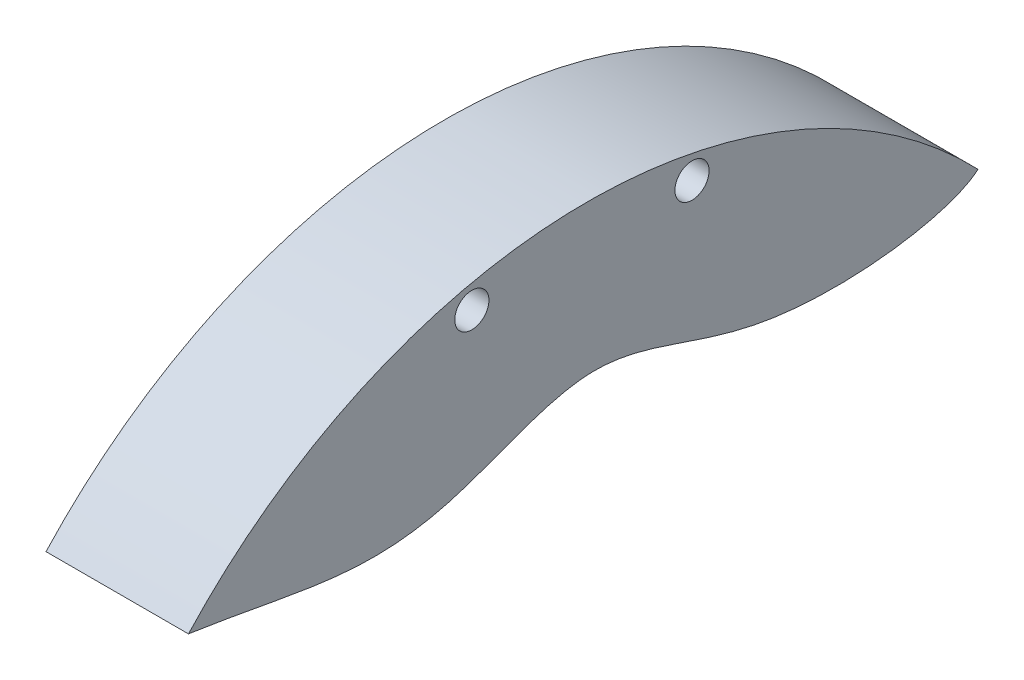
SolidWorks part; units mm, degrees
ref_plane "Front Plane" through (0, 0, 0) normal (0, 0, 1) x (1, 0, 0)
ref_plane "Top Plane" through (0, 0, 0) normal (0, 1, 0) x (1, 0, 0)
ref_plane "Right Plane" through (0, 0, 0) normal (1, 0, 0) x (0, 0, -1)
sketch "Sketch3" plane through (0, 0, 0) normal (1, 0, 0) x (0, 0, -1)
  line L0 (-105.0442, 0) -> (95, 0) construction
  line L1 (0, 119.9399) -> (0, 65.003) construction
  line L2 (-105.0486, 63.9943) -> (119.6551, 66.1519) construction
  arc A3 (68.6547, 65.6622) -> (-69.903, 64.3318) centre (0, 0) ccw
  spline S0 degree 3 poles (-69.903, 64.3318) (-49.9212, 61.3953) (-33.7665, 55.0463) (1.4901, 72.5654) (17.3176, 64.3363) (43.3327, 58.3883) (63.9174, 61.408) (68.6547, 65.6622) knots 0 0 0 0 0.370229 0.525676 0.698471 0.745904 1 1 1 1
  point P10 (0, 0)
  dimension "D3" = 65
extrude "Boss-Extrude1" add sketch "Sketch3" along normal blind 25
shell "Shell1" thickness 5 removed face at (12.5, 64.6644, 35.2635)
sketch "Sketch4" plane through (25, 0, 0) normal (1, 0, 0) x (0, 0, -1)
  line L0 (-69.903, 64.3318) -> (68.6547, 65.6622) construction
  line L1 (-0.6241, 64.997) -> (-0.9122, 94.9956) construction
  arc A0 (68.6547, 65.6622) -> (-69.903, 64.3318) centre (0, 0) ccw construction
  circle A1 centre (-20.1716, 88.6816) radius 3
  circle A2 centre (18.465, 89.0526) radius 3
  dimension "D1" = 6
extrude "Cut-Extrude1" cut sketch "Sketch4" against normal blind 38
sketch "Sketch5" plane through (0, 0, 0) normal (-1, 0, 0) x (0, 0, 1)
  line L0 (-50.5284, 60.5786) -> (-2.1664, 68.7032) construction
  line L1 (-2.1664, 68.7032) -> (50.0977, 60.9353) construction
  arc A0 (50.0977, 60.9353) -> (-50.5284, 60.5786) centre (0, 0) ccw
  spline S0 degree 3 poles (69.903, 64.3318) (49.9212, 61.3953) (33.7665, 55.0463) (-1.4901, 72.5654) (-17.3176, 64.3363) (-43.3327, 58.3883) (-63.9174, 61.408) (-68.6547, 65.6622) knots 0 0 0 0 0.370229 0.525676 0.698471 0.745904 1 1 1 1 construction
  spline S1 degree 3 poles (-50.5284, 60.5786) (-38.195, 60.1296) (-26.5289, 61.5095) (-10.0455, 68.1943) (7.3254, 69.4293) (18.7694, 61.9805) (35.7395, 59.3719) (45.2846, 59.7438) (50.0977, 60.9353) knots 0 0 0 0 0.144444 0.387007 0.452522 0.734078 0.792346 1 1 1 1
extrude "Boss-Extrude2" add sketch "Sketch5" along normal blind 5
fillet "Fillet1" radius 2 1 edges at (0, 78.8848, -0.2796)
ref_plane "Plane1" through (5, 0, 0) normal (1, 0, 0) x (0, 0, -1)
